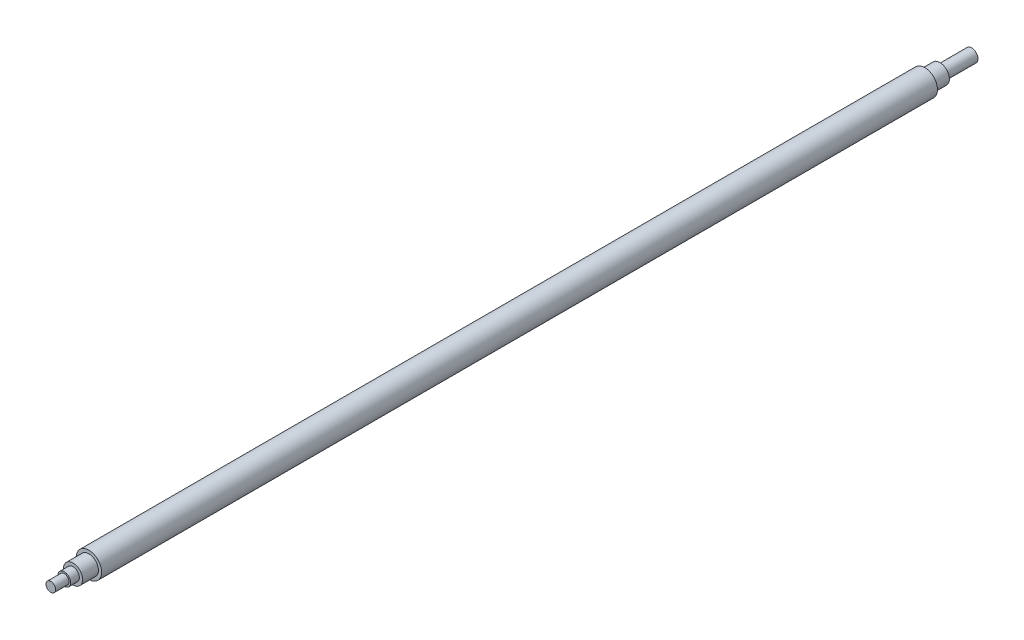
SolidWorks part; units mm, degrees
ref_plane "Piano frontale" through (0, 0, 0) normal (0, 0, 1) x (1, 0, 0)
ref_plane "Piano superiore" through (0, 0, 0) normal (0, 1, 0) x (1, 0, 0)
ref_plane "Piano destro" through (0, 0, 0) normal (1, 0, 0) x (0, 0, -1)
sketch "Schizzo2" plane through (0, 0, 0) normal (1, 0, 0) x (0, 0, -1)
  line L0 (8.5, 0) -> (8.5, 3)
  line L1 (8.5, 3) -> (17, 3)
  line L2 (17, 3) -> (17, 4)
  line L3 (17, 4) -> (22.5, 4)
  line L4 (22.5, 4) -> (22.5, 6)
  line L5 (22.5, 6) -> (32.5, 6)
  line L6 (32.5, 6) -> (32.5, 8)
  line L7 (32.5, 8) -> (558.5, 8)
  line L8 (558.5, 8) -> (558.5, 6)
  line L9 (558.5, 6) -> (568, 6)
  line L10 (568, 6) -> (568, 4)
  line L11 (588, 0) -> (8.5, 0)
  line L14 (588, 0) -> (588, 4)
  line L15 (0, 0) -> (351.0218, 0) construction
  line L18 (568, 4) -> (588, 4)
  point P33 (0, 0)
  dimension "D2" = 6
  dimension "D3" = 8
  dimension "D4" = 12
  dimension "D5" = 16
  dimension "D6" = 12
  dimension "D7" = 8
  dimension "D8" = 8.5
  dimension "D9" = 5.5
  dimension "D10" = 10
  dimension "D11" = 526
  dimension "D12" = 9.5
  dimension "D13" = 20
revolve "Rivoluzione2" add sketch "Schizzo2" angle 360 about L15
